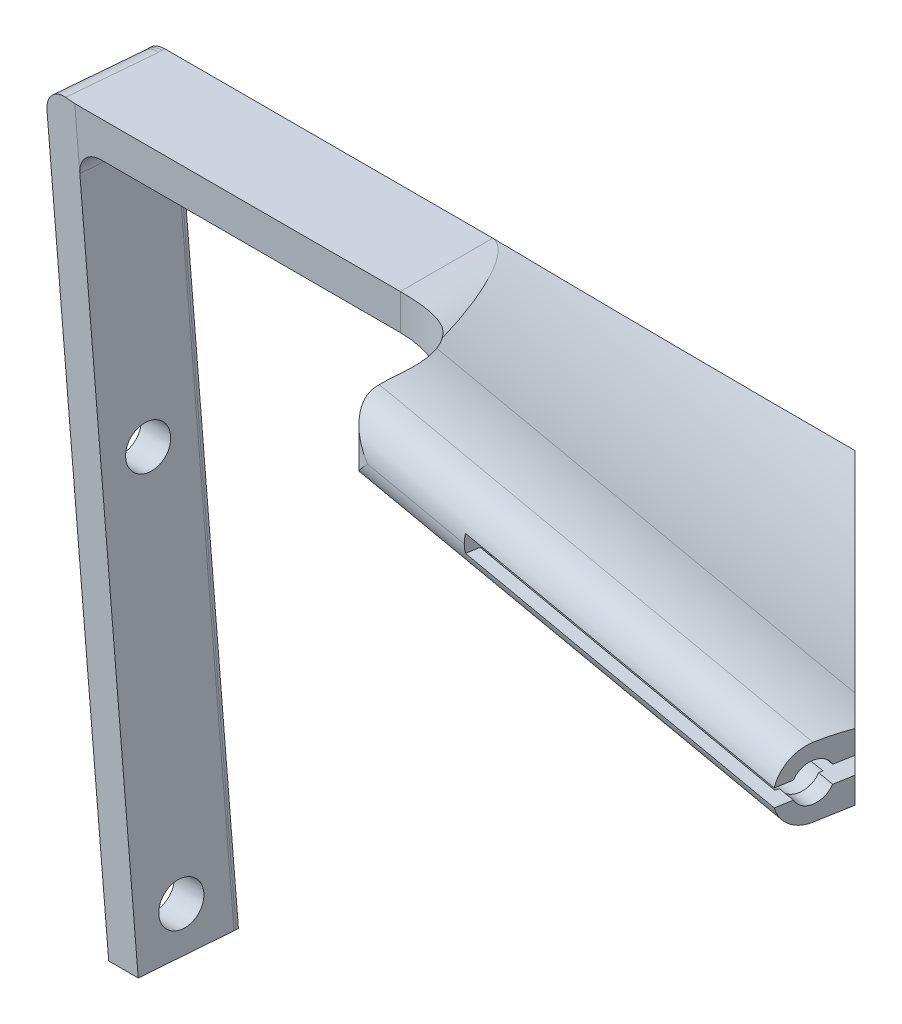
SolidWorks part; units mm, degrees
ref_plane "Front Plane" through (0, 0, 0) normal (0, 0, 1) x (1, 0, 0)
ref_plane "Top Plane" through (0, 0, 0) normal (0, 1, 0) x (1, 0, 0)
ref_plane "Right Plane" through (0, 0, 0) normal (1, 0, 0) x (0, 0, -1)
sketch "Sketch1" plane through (0, 0, 0) normal (0, 0, 1) x (1, 0, 0)
  line L0 (0, 0) -> (76.2, 0)
  line L1 (76.2, 0) -> (76.2, -5.08)
  line L2 (76.2, -5.08) -> (2.8536, -5.08)
  line L3 (2.8536, -5.08) -> (7.2811, -55.6867)
  line L4 (7.2811, -55.6867) -> (4.8903, -55.8959)
  line L5 (4.8903, -55.8959) -> (0, 0)
  dimension "D1" = 5.08
  dimension "length1" = 76.2
  dimension "D3" = 2.4
  dimension "D4" = 85
  dimension "D5" = 50.8
extrude "OverallGeometry-Boss-Extrude1" add sketch "Sketch1" along normal blind 0.254
sketch "Sketch2" plane through (4.8903, -55.8959, 0) normal (0.0872, -0.9962, 0) x (0.9962, 0.0872, 0)
  line L0 (2.4, 0.254) -> (1.8283, 6.7882)
  line L1 (1.8283, 6.7882) -> (-0.5534, 6.5798)
  line L2 (-0.5534, 6.5798) -> (0, 0.254)
  line L3 (0, 0.254) -> (2.4, 0.254) construction
  line L4 (0, 0.254) -> (2.4, 0.254)
  line L5 (2.4, 0.254) -> (75.4673, 0.254) construction
  dimension "D1" = 6.35
  dimension "D2" = 95
extrude "CameraPitch-Boss-Extrude2" add sketch "Sketch2" against normal up to vertex (56.1094 mm away) up to point (0, 0, 0.254)
sketch "Sketch4" plane through (0, -5.08, 0) normal (0, -1, 0) x (1, 0, 0)
  line L0 (76.2, 0.254) -> (71.7893, 25.2681)
  line L1 (-1.9886, 6.7882) -> (33.5714, 6.7882)
  line L2 (2.8536, 0.254) -> (76.2, 0.254) construction
  line L3 (7.2811, 0.254) -> (6.7116, 6.7882) construction
  line L7 (-1.4191, 0) -> (-1.4191, 0.254)
  line L8 (-1.4191, 0.254) -> (-1.9886, 6.7882)
  line L10 (-1.4191, 0) -> (76.2, 0)
  line L11 (76.2, 0) -> (76.2, 0.254)
  line L12 (33.5714, 6.7882) -> (33.5714, 18.5293)
  line L13 (33.5714, 18.5293) -> (71.7893, 25.2681)
  dimension "D1" = 80
  dimension "D2" = 25.4
  dimension "D3" = 35.56
  dimension "D4" = 3.81
extrude "Boss-Extrude3" add sketch "Sketch4" against normal up to surface (5.08 mm away) up to face at (30.9618, 0, 0.1524)
sketch "Sketch3" plane through (2.3947, 0.2095, 0.2103) normal (0.9924, 0.0868, 0.0872) x (0.1097, -0.3046, -0.9461)
  line L0 (14.3063, -54.3631) -> (13.3284, -51.3959) construction
  line L1 (17.5204, -53.3038) -> (11.2908, -55.3568) construction
  line L2 (13.3284, -51.3959) -> (4.5833, -24.8597) construction
  line L4 (-4.6251, -7.0618) -> (11.2908, -55.3568) construction
  circle A0 centre (4.5833, -24.8597) radius 1.524
  circle A1 centre (13.3284, -51.3959) radius 1.524
  dimension "D4" = 3.048
  dimension "D1" = 27.94
  dimension "D2" = 3.1242
  dimension "D3" = 3.175
extrude "Cut-Extrude1" cut sketch "Sketch3" against normal through all
sketch "Sketch5" plane through (73.9457, 0, 13.0386) normal (0.9848, 0, 0.1736) x (0.1736, 0, -0.9848)
  line L0 (-12.4182, -2.54) -> (-9.8782, -2.54) construction
  line L1 (-12.4182, 0) -> (-12.4182, -5.08) construction
  line L2 (-12.4182, -1.905) -> (-11.4022, -1.905)
  line L3 (-12.4182, -3.175) -> (-11.4022, -3.175)
  line L4 (-12.4182, -3.175) -> (-12.4182, -1.905)
  line L5 (-8.3542, -1.905) -> (-4.5442, -1.905)
  line L6 (-4.5442, -1.905) -> (-4.5442, -3.175)
  line L7 (-4.5442, -3.175) -> (-8.3542, -3.175)
  arc A0 (-11.4022, -3.175) -> (-8.3542, -3.175) centre (-9.8782, -2.54) ccw
  arc A1 (-8.3542, -1.905) -> (-11.4022, -1.905) centre (-9.8782, -2.54) ccw
  dimension "D1" = 3.302
  dimension "D2" = 2.54
  dimension "D3" = 1.27
  dimension "D4" = 3.81
extrude "Cut-Extrude2" cut sketch "Sketch5" against normal blind 27.94
sketch "Sketch6" plane through (73.9457, 0, 13.0386) normal (0.9848, 0, 0.1736) x (0.1736, 0, -0.9848)
  line L0 (-11.4022, -1.905) -> (-11.1225, -1.905)
  line L1 (-8.3542, -1.905) -> (-8.6338, -1.905)
  line L2 (-8.3542, -3.175) -> (-8.6338, -3.175)
  line L3 (-11.4022, -3.175) -> (-11.1225, -3.175)
  line L4 (-12.4182, -3.175) -> (-11.4022, -3.175) construction
  line L5 (-4.5442, -1.905) -> (-8.3542, -1.905) construction
  arc A0 (-11.4022, -3.175) -> (-8.3542, -3.175) centre (-9.8782, -2.54) ccw
  arc A2 (-11.1225, -3.175) -> (-8.6338, -3.175) centre (-9.8782, -2.54) ccw
  arc A3 (-8.6338, -1.905) -> (-11.1225, -1.905) centre (-9.8782, -2.54) ccw
  arc A4 (-8.3542, -1.905) -> (-11.4022, -1.905) centre (-9.8782, -2.54) ccw
  dimension "D1" = 0.254
extrude "Boss-Extrude4" add sketch "Sketch6" against normal blind 1.27
sketch "Sketch8" plane through (4.8903, -55.8959, 0) normal (0.0872, -0.9962, 0) x (0.9962, 0.0872, 0)
  line L0 (1.8283, 6.7882) -> (-0.5534, 6.5798)
  line L1 (-0.5534, 6.5798) -> (0, 0.254)
  line L2 (0, 0.254) -> (0, 0)
  line L3 (0, 0) -> (-7.3483, 0)
  line L4 (-7.3483, 0) -> (-7.3483, 6.7882)
  line L5 (-7.3483, 6.7882) -> (1.8283, 6.7882)
extrude "Cut-Extrude4" cut sketch "Sketch8" against normal through all
sketch "Sketch9" plane through (0, 0, 0) normal (0, 1, 0) x (1, 0, 0)
  line L0 (72.6935, -20.1402) -> (52.5533, 0)
  line L1 (71.7893, -25.2681) -> (76.2, -0.254) construction
  line L2 (76.2, 0) -> (0, 0) construction
  line L3 (52.5533, 0) -> (76.2, 0)
  line L4 (76.2, 0) -> (76.2, -20.1402)
  line L5 (76.2, -20.1402) -> (72.6935, -20.1402)
  dimension "D1" = 45
  dimension "D2" = 5.207
extrude "Cut-Extrude5" cut sketch "Sketch9" against normal through all
fillet "Fillet1" radius 2.54 1 edges at (33.5714, -2.54, 18.5293)
fillet "Fillet2" radius 7.62 1 edges at (33.5714, -2.54, 6.7882)
sketch "Sketch10" plane through (73.9457, 0, 13.0386) normal (0.9848, 0, 0.1736) x (0.1736, 0, -0.9848)
  line L0 (9.1258, 0) -> (9.1258, 48.4539) construction
  circle A0 centre (9.1258, 48.4539) radius 51.1339
  point P4 (9.1258, -2.68)
  dimension "D1" = 2.4
extrude "Cut-Extrude6" cut sketch "Sketch10" against normal through all
fillet "Fillet3" radius 2.54 2 edges at (53.7298, -5.08, 22.0837) (53.7298, 0, 22.0837) tangent propagation no
fillet "Fillet4" radius 17.78 1 edges at (53.0863, 0, 16.6829)
sketch "Sketch13" plane through (0, 0, 6.7882) normal (0, 0, 1) x (1, 0, 0)
  line L0 (-24.8486, 10.2291) -> (25.9514, 10.2291) construction
  line L1 (-24.8486, 22.9291) -> (25.9514, 22.9291)
  line L2 (-24.8486, -2.4709) -> (25.9514, -2.4709)
  line L3 (25.9514, -5.08) -> (25.9514, -1.4148) construction
  arc A0 (-24.8486, 22.9291) -> (-24.8486, -2.4709) centre (-24.8486, 10.2291) ccw
  arc A1 (25.9514, -2.4709) -> (25.9514, 22.9291) centre (25.9514, 10.2291) ccw
  ellipse E0 centre (52.5533, 48.4539) end of major axis (347.0218, 48.4539) minor radius 51.1339 (0.1631, -1.8642) -> (52.5533, -2.68) ccw construction
  point P2 (0.5514, 10.2291)
  dimension "D2" = 12.7
  dimension "D1" = 50.8
extrude "Cut-Extrude8" cut sketch "Sketch13" against normal through all and the other way through all
fillet "Fillet14" radius 1.524 1 edges
fillet "Fillet15" radius 1.524 3 edges at (2.8522, -5.08, 0.2539)
fillet "Fillet16" radius 1.524 1 edges at (2.5532, -29.1834, 0.254)
fillet "Fillet17" radius 1.524 3 edges at (0.2162, -2.4709, 0.0937) (0.2147, -2.4709, 0.2539) (-0.0645, -2.4709, 3.4501)
